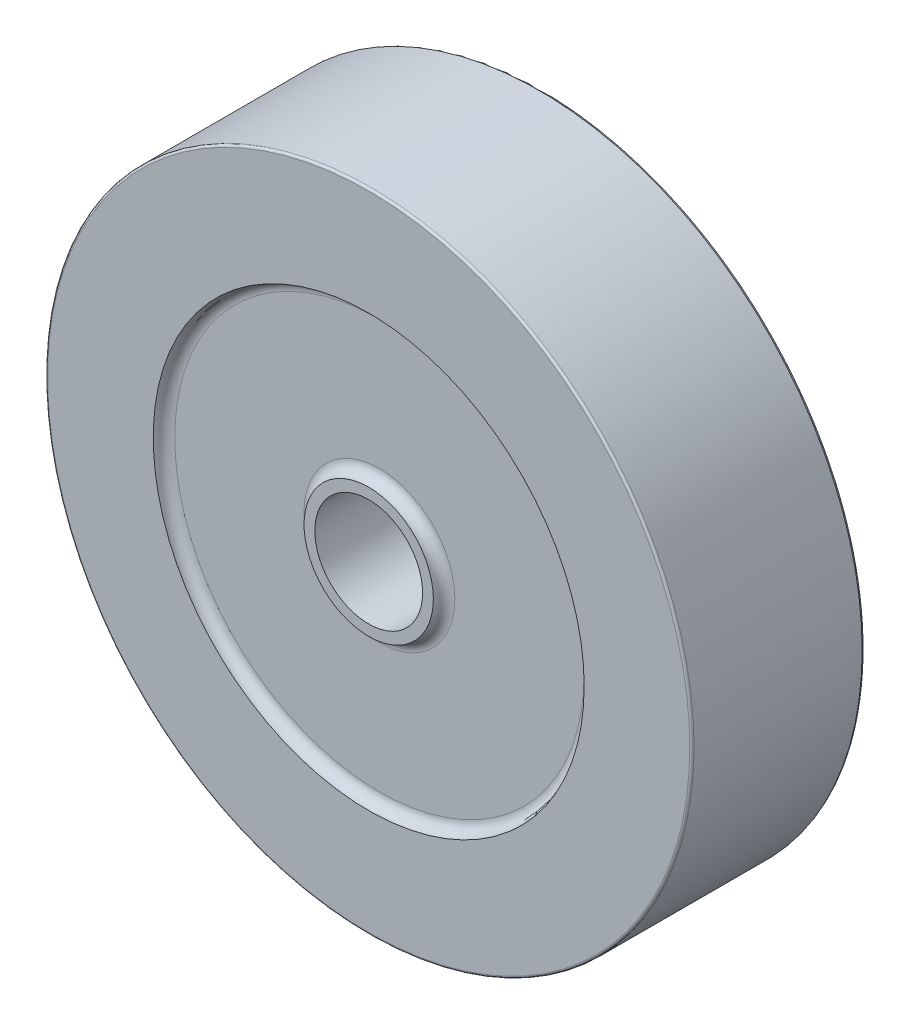
SolidWorks part; units mm, degrees
ref_plane "Front Plane" through (0, 0, 0) normal (0, 0, 1) x (1, 0, 0)
ref_plane "Top Plane" through (0, 0, 0) normal (0, 1, 0) x (1, 0, 0)
ref_plane "Right Plane" through (0, 0, 0) normal (1, 0, 0) x (0, 0, -1)
sketch "Sketch2" plane through (0, 0, 0) normal (1, 0, 0) x (0, 0, -1)
  line L0 (0, -7.62) -> (1.27, -7.62)
  line L1 (0, 0) -> (20.32, 0)
  line L2 (0, 0) -> (0, -7.62)
  line L3 (0, -38.1) -> (20.32, -38.1)
  line L4 (20.32, 0) -> (20.32, -11.43)
  line L5 (1.27, -7.62) -> (1.27, -25.4)
  line L6 (1.27, -25.4) -> (0, -25.4)
  line L7 (0, -25.4) -> (0, -38.1)
  line L8 (10.16, 0) -> (10.16, -38.1) construction
  line L9 (20.32, -11.43) -> (19.05, -11.43)
  line L10 (19.05, -11.43) -> (19.05, -25.4)
  line L11 (19.05, -25.4) -> (20.32, -25.4)
  line L12 (20.32, -25.4) -> (20.32, -38.1)
  dimension "D1" = 38.1
  dimension "D2" = 7.62
  dimension "D3" = 12.7
  dimension "D4" = 1.27
  dimension "D5" = 20.32
  dimension "D6" = 11.43
revolve "Revolve1" add sketch "Sketch2" angle 360 about L1
sketch "Sketch3" plane through (0, 0, 0) normal (0, 0, 1) x (1, 0, 0)
  circle A0 centre (0, 0) radius 6.35
  dimension "D1" = 12.7
extrude "Cut-Extrude1" cut sketch "Sketch3" against normal through all contours A0
fillet "Fillet1" radius 1.27 4 edges at (11.43, 0, -19.05) (25.4, 0, -19.05) (7.62, 0, -1.27) (25.4, 0, -1.27)
fillet "Fillet2" radius 0.254 2 edges at (38.1, 0, 0) (38.1, 0, -20.32)
sketch "Sketch4" plane through (0, 0, -20.32) normal (0, 0, -1) x (-1, 0, 0)
  line L1 (-6.35, -6.35) -> (6.35, -6.35)
  line L2 (-6.35, -6.35) -> (-6.35, 6.35)
  line L3 (-6.35, 6.35) -> (6.35, 6.35)
  line L4 (6.35, -6.35) -> (6.35, 6.35)
  circle A1 centre (0, 0) radius 6.35 construction
extrude "Cut-Extrude2" cut sketch "Sketch4" against normal blind 5.08
